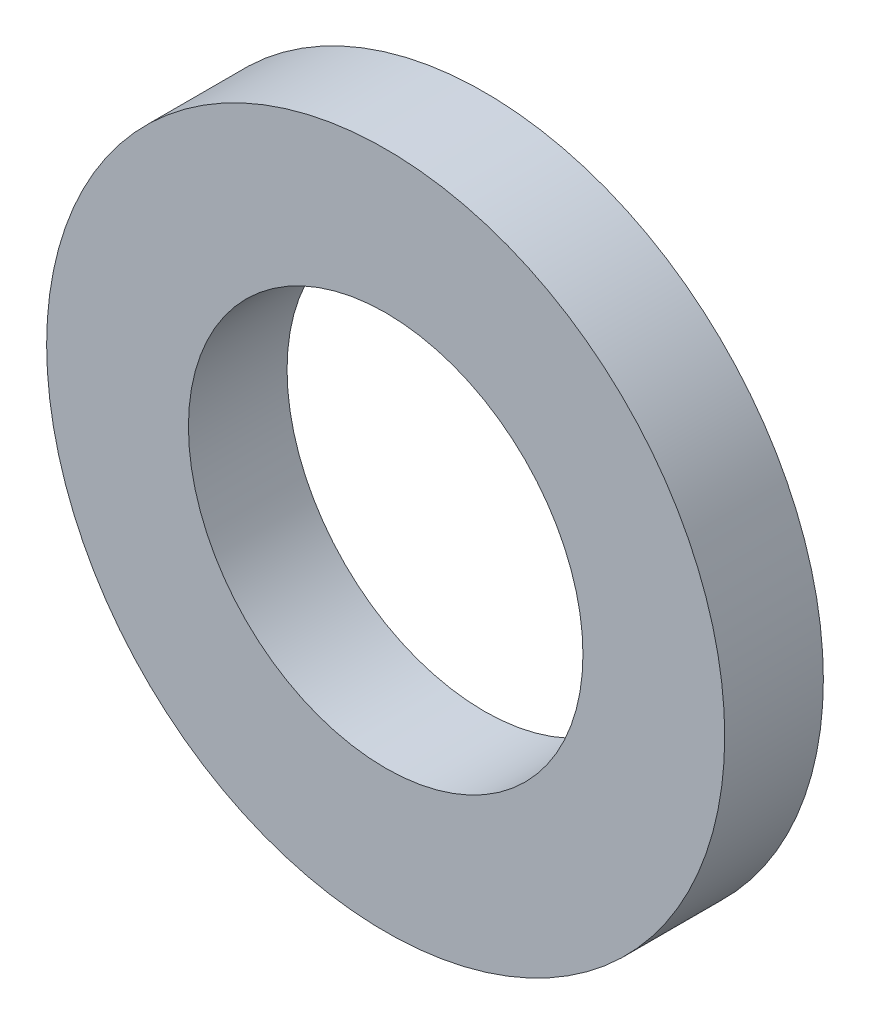
SolidWorks part; units mm, degrees
ref_plane "Top" through (0, 0, 0) normal (0, 0, 1) x (1, 0, 0)
ref_plane "Front" through (0, 0, 0) normal (0, 1, 0) x (1, 0, 0)
ref_plane "Right" through (0, 0, 0) normal (1, 0, 0) x (0, 0, -1)
sketch "Top Sketch" plane through (0, 0, 0) normal (0, 0, 1) x (1, 0, 0)
  circle A0 centre (0, 0) radius 3.2
  circle A1 centre (0, 0) radius 5.5
  dimension "Inside Diameter" = 6.4
  dimension "Outside Diameter" = 11
extrude "Extrude Thickness" add sketch "Top Sketch" along normal blind 1.6
equation "\"M2 Close Fit Hole\"= 2.2"
equation "\"M2.5 Close Fit Hole\"= 2.7"
equation "\"M3 Close Fit Hole\"= 3.2"
equation "\"M4 Close Fit Hole\"= 4.3"
equation "\"M5 Close Fit Hole\"= 5.3"
equation "\"M6 Close Fit Hole\"= 6.3"
equation "\"M7 Close Fit Hole\"= 7.4"
equation "\"M8 Close Fit Hole\"= 8.4"
equation "\"M2 Tap Hole 75%\"= 1.6"
equation "\"M3 Tap Hole 75%\"= 2.5"
equation "\"M4 Tap Hole 75%\"= 3.3"
equation "\"M5 Tap Hole 75%\"= 4.2"
equation "\"M6 Tap Hole 75%\"= 5"
equation "\"M7 Tap Hole 75%\"= 6"
equation "\"M8 Tap Hole 75%\"= 6.8"
